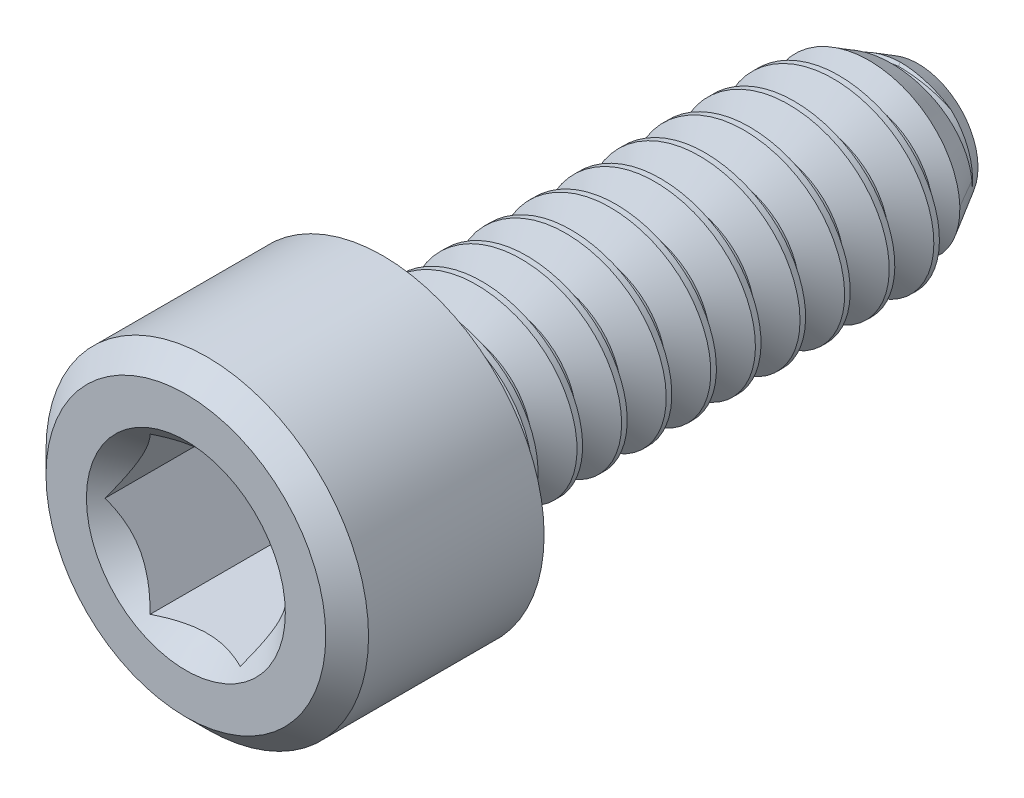
SolidWorks part; units mm, degrees
ref_plane "Front Plane" through (0, 0, 0) normal (0, 0, 1) x (1, 0, 0)
ref_plane "Top Plane" through (0, 0, 0) normal (0, 1, 0) x (1, 0, 0)
ref_plane "Right Plane" through (0, 0, 0) normal (1, 0, 0) x (0, 0, -1)
sketch "Sketch2" plane through (0, 0, 0) normal (0, 0, 1) x (1, 0, 0)
  circle A0 centre (0, 0) radius 1.7145
  dimension "D1" = 3.429
curve "Helix/Spiral1" pitch 0.7937 height 50.8 radius 1.7145 centre (0, 0, 0) axis (0, 0, 1) start towards (0, 1, 0) parameters "TPI LENGTH"=50.8, "PITCH"=0.7937
sketch "Sketch3" plane through (0, 0, 0) normal (1, 0, 0) x (0, 0, -1)
  line L0 (0.0496, 1.7145) -> (-0.0496, 1.7145)
  line L1 (-0.0496, 1.7145) -> (-0.3473, 1.1989)
  line L2 (-0.3473, 1.1989) -> (0.3473, 1.1989)
  line L3 (0.3473, 1.1989) -> (0.0496, 1.7145)
  line L4 (0, 0) -> (0, 1.7145) construction
  line L5 (-0.1984, 1.4567) -> (0.1984, 1.4567) construction
  line L6 (0, 1.7145) -> (0, -1.7145) construction
  line L7 (0, 1.8004) -> (0.3969, 1.8004) construction
  line L8 (0.3969, 1.8004) -> (0.3969, 1.113) construction
  line L9 (0.3969, 1.113) -> (1.5998, 3.1966) construction
  line L10 (-0.9361, 1.7145) -> (-0.9361, 1.1989) construction
  dimension "D1" = 60
  dimension "D2" = 30
  dimension "D3" = 0.6874
  dimension "pitch*.125" = 0.0992
  dimension "D4" = 0.5156
  dimension "pitch*.5" = 0.3969
  dimension "1/2pitch" = 0.3969
sweep "Sweep1" add profiles "Sketch3" path "Helix/Spiral1"
sketch "Sketch22" plane through (0, 0, 0) normal (1, 0, 0) x (0, 0, -1)
  line L0 (0.0496, 1.7145) -> (-0.0496, 1.7145) construction
  line L1 (0.0496, 1.7145) -> (-0.0496, 1.7145)
sketch "Sketch4" plane through (0, 0, 0) normal (1, 0, 0) x (0, 0, -1)
  line L0 (-1.9435, 0.508) -> (0.436, 0.508) construction
  line L4 (0.3473, 1.1989) -> (0.0496, 1.7145)
  line L5 (-0.3473, 1.1989) -> (0.3473, 1.1989)
  line L6 (-0.0496, 1.7145) -> (-0.3473, 1.1989)
  line L7 (0.0496, 1.7145) -> (-0.0496, 1.7145)
  line L8 (0.3473, 1.1989) -> (0.0496, 1.7145)
  line L9 (-0.3473, 1.1989) -> (0.3473, 1.1989)
  line L10 (-0.0496, 1.7145) -> (-0.3473, 1.1989)
  line L11 (0.0496, 1.7145) -> (-0.0496, 1.7145)
  dimension "D2" = 0.508
  dimension "D1" = 0
revolve "Revolve1" add sketch "Sketch4" angle 360 about L0
sketch "Sketch5" plane through (0, 0, 0) normal (1, 0, 0) x (0, 0, -1)
  line L0 (0, 0) -> (3.5657, 0) construction
  line L2 (0, 0) -> (-51.1473, 0)
  line L3 (0, 0) -> (0, 1.1989)
  line L4 (0, 1.1989) -> (-51.1473, 1.1989)
  line L5 (-51.1473, 0) -> (-51.1473, 1.1989)
revolve "Revolve2" add sketch "Sketch5" angle 360 about L0
sketch "Sketch7" plane through (0, 0, 0) normal (1, 0, 0) x (0, 0, -1)
  line L0 (0, 1.0668) -> (-3.4315, 3.048)
  line L1 (-3.4315, 3.048) -> (0.762, 3.048)
  line L2 (0.762, 3.048) -> (0.762, 0)
  line L3 (0, 1.0668) -> (0, 0)
  line L4 (0, 0) -> (0.762, 0)
  line L5 (0, 0) -> (11.6435, 0) construction
  dimension "D1" = 30
  dimension "D2" = 1.0668
  dimension "D3" = 3.048
  dimension "D4" = 0.762
revolve "Cut-Revolve1" cut sketch "Sketch7" angle 360 about L5
sketch "Sketch10" plane through (0, 0, 0) normal (1, 0, 0) x (0, 0, -1)
  line L0 (0, 3.1572) -> (0, -3.1572) construction
  line L1 (-85.725, -9.525) -> (-9.525, -9.525)
  line L2 (-85.725, -9.525) -> (-85.725, 9.525)
  line L3 (-85.725, 9.525) -> (-9.525, 9.525)
  line L4 (-9.525, -9.525) -> (-9.525, 9.525)
  line L6 (-9.525, 0) -> (-21.2921, 0) construction
  line L7 (3.1572, 0) -> (-3.1572, 0) construction
  point P7 (0, 0)
  dimension "D1" = 76.2
  dimension "D2" = 9.525
  dimension "D3" = 19.05
extrude "Cut-Extrude3" cut sketch "Sketch10" against normal through all and the other way through all
sketch "Sketch17" plane through (0, 0, 9.525) normal (0, 0, 1) x (1, 0, 0)
  circle A0 centre (0, 0) radius 2.8702
  dimension "D1" = 5.7404
extrude "Extrude2" add sketch "Sketch17" along normal blind 12.7
sketch "Sketch18" plane through (0, 0, 0) normal (1, 0, 0) x (0, 0, -1)
  line L0 (0, 0) -> (-21.4476, 0) construction
  line L1 (-9.525, 2.8702) -> (-22.225, 2.8702) construction
  line L2 (-9.525, -2.8702) -> (-9.525, 2.8702) construction
  line L3 (-22.225, 2.8702) -> (-22.225, -2.8702) construction
  line L4 (-13.0302, 0) -> (-13.0302, 2.8702)
  line L5 (-13.0302, 2.8702) -> (-22.479, 2.8702)
  line L6 (-22.479, 2.8702) -> (-22.479, 0)
  line L7 (-22.479, 0) -> (-13.0302, 0)
  dimension "D2" = 3.5052
  dimension "D3" = 0.254
revolve "Cut-Revolve3" cut sketch "Sketch18" angle 360 about L0
sketch "Sketch19" plane through (0, 0, 13.0302) normal (0, 0, 1) x (1, 0, 0)
  line L1 (0.802, -1.3891) -> (1.604, 0)
  line L2 (1.604, 0) -> (0.802, 1.3891)
  line L3 (0.802, 1.3891) -> (-0.802, 1.3891)
  line L4 (-0.802, 1.3891) -> (-1.604, 0)
  line L5 (-1.604, 0) -> (-0.802, -1.3891)
  line L6 (-0.802, -1.3891) -> (0.802, -1.3891)
  circle A0 centre (0, 0) radius 1.3891 construction
  dimension "D1" = 2.7781
extrude "Cut-Extrude4" cut sketch "Sketch19" against normal blind 2.413
sketch "Sketch20" plane through (0, 0, 0) normal (-1, 0, 0) x (0, 1, 0)
  line L0 (-1.3891, -10.6172) -> (-1.3891, -13.0302) construction
  line L1 (0, -10.3089) -> (0, 1.1556) construction
  line L2 (0, 0) -> (0, -51.1473) construction
  line L3 (0, 0) -> (0, 3.5657) construction
  line L4 (-1.7701, -13.0302) -> (-1.3891, -12.6492)
  line L6 (-2.8702, -13.0302) -> (2.8702, -13.0302) construction
  line L7 (-1.3891, -12.6492) -> (-1.3891, -10.6172)
  line L8 (-1.3891, -10.6172) -> (0, -9.7826)
  line L9 (0, -9.7826) -> (0, -13.0302)
  line L10 (0, -13.0302) -> (-1.7701, -13.0302)
  line L11 (0, -10.6172) -> (-1.3891, -10.6172) construction
  dimension "D1" = 59
  dimension "D2" = 45
  dimension "D3" = 0.381
revolve "Cut-Revolve5" cut sketch "Sketch20" angle 360 about L1
chamfer "Chamfer1" distance 0.381 angle 45 1 edges at (-2.8702, 0, 13.0302)
